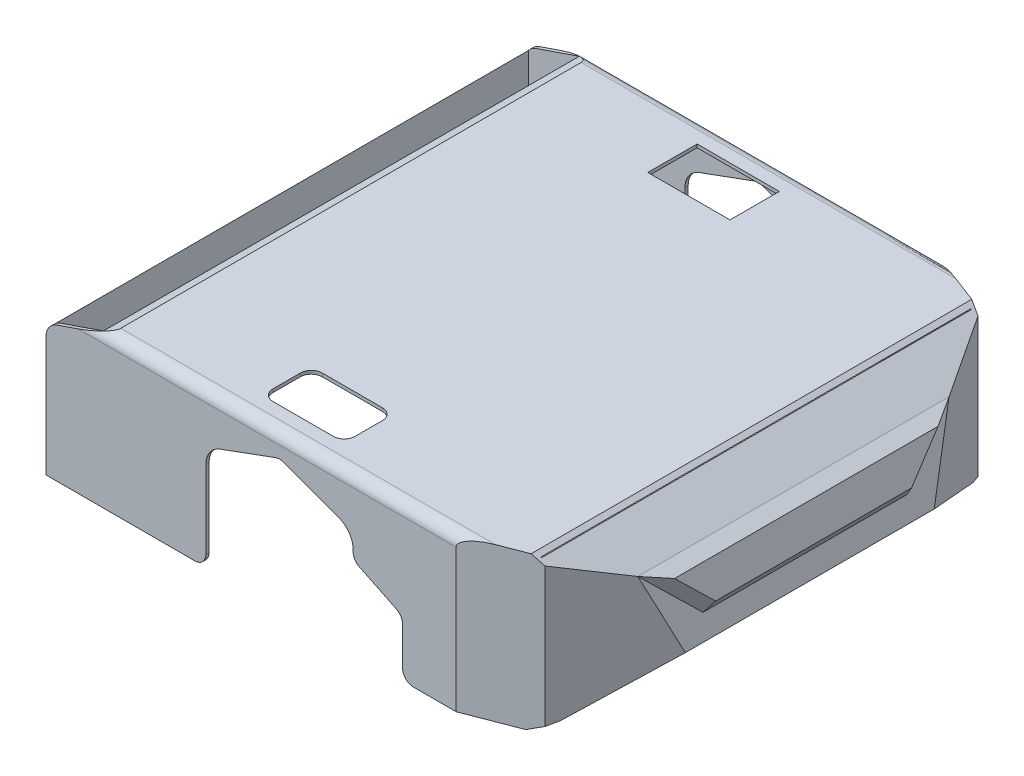
SolidWorks part; units mm, degrees
material "CA"
ref_plane "Front Plane" through (0, 0, 0) normal (0, 0, 1) x (1, 0, 0)
ref_plane "Top Plane" through (0, 0, 0) normal (0, 1, 0) x (1, 0, 0)
ref_plane "Right Plane" through (0, 0, 0) normal (1, 0, 0) x (0, 0, -1)
sketch "Sketch1" plane through (0, 0, 0) normal (0, 0, 1) x (1, 0, 0)
  line L1 (0, 0) -> (480, 0)
  line L2 (0, 0) -> (0, 140)
  line L3 (0, 140) -> (480, 140)
  line L4 (480, 0) -> (480, 140)
  dimension "D1" = 480
  dimension "D2" = 140
extrude "Boss-Extrude1" add sketch "Sketch1" along normal blind 440
sketch "Sketch2" plane through (0, 0, 440) normal (0, 0, 1) x (1, 0, 0)
  line L1 (0, 0) -> (420, 0)
  line L2 (0, 0) -> (0, 120)
  line L3 (0, 120) -> (420, 120)
  line L4 (420, 0) -> (420, 120)
  dimension "D1" = 120
  dimension "D2" = 420
sketch "Sketch3" plane through (0, 0, 440) normal (0, 0, 1) x (1, 0, 0)
  line L0 (0, 120) -> (58.2254, 140)
  line L1 (480, 140) -> (0, 140) construction
  line L2 (58.2254, 140) -> (423.4831, 140)
  line L3 (423.4831, 140) -> (461.8504, 111.6906)
  line L4 (461.8504, 111.6906) -> (480, 30.0603)
  line L5 (480, 0) -> (480, 140) construction
  line L6 (480, 30.0603) -> (420, 0)
  line L7 (0, 120) -> (0, 186.0028)
  line L8 (0, 186.0028) -> (591.5196, 186.0028)
  line L9 (591.5196, 186.0028) -> (591.5196, 0)
  line L10 (591.5196, 0) -> (420, 0)
  line L11 (480, 140) -> (0, 140) construction
extrude "Cut-Extrude2" cut sketch "Sketch3" against normal through all
chamfer "Chamfer1" distance 15 angle 60 1 edges at (480, 30.0603, 220) first distance on face at (470.9252, 70.8754, 220)
sketch "Sketch4" plane through (0, 140, 0) normal (0, 1, 0) x (1, 0, 0)
  line L2 (476.7444, -333.5325) -> (476.7444, -106.4675)
  line L5 (374.147, -440) -> (432.7602, -417.4465)
  line L7 (432.7602, -417.4465) -> (476.7444, -333.5325)
  line L8 (476.7444, -333.5325) -> (476.7444, -220)
  line L9 (476.7444, -440) -> (476.7444, 0) construction
  line L10 (476.7444, -333.5325) -> (476.7444, -220)
  line L11 (476.7444, -220) -> (259.9754, -220) construction
  line L13 (374.147, -440) -> (571.4453, -440)
  line L14 (571.4453, -440) -> (571.4453, 0)
  line L15 (571.4453, 0) -> (374.147, 0)
  line L16 (374.147, 0) -> (432.7602, -22.5535)
  line L17 (432.7602, -22.5535) -> (476.7444, -106.4675)
  line L18 (423.4831, 0) -> (58.2254, 0) construction
  point P14 (476.7444, -220)
extrude "Cut-Extrude3" cut sketch "Sketch4" against normal blind 335 contours L2 L17 L16 L15 L14 L13 L5 L7
fillet "Fillet1" radius 10 2 edges at (216.1862, 140, 0) (216.1862, 140, 440)
fillet "Fillet2" radius 15 1 edges at (0, 120, 220)
sketch "Sketch6" plane through (463.7578, 103.1116, 0) normal (0.9762, 0.217, 0) x (0, 0, -1)
  line L0 (-361.9476, 8.7884) -> (-313.0975, -39.8352)
  line L1 (-313.0975, -39.8352) -> (-126.9025, -39.8352)
  line L2 (-361.9476, 8.7884) -> (-78.0524, 8.7884)
  line L3 (-333.5325, -59.8352) -> (-106.4675, -59.8352)
  line L4 (-220, -59.8352) -> (-220, -40.6647) construction
  line L5 (-78.0524, 8.7884) -> (-361.9476, 8.7884) construction
  line L6 (-78.0524, 8.7884) -> (-126.9025, -39.8352)
  point P10 (-220, -39.8352)
  point P15 (-220, 8.7884)
  line M9 (-78.0524, 8.7884) -> (-361.9476, 8.7884)
  dimension "D1" = 20
extrude "Boss-Extrude2" add sketch "Sketch6" along direction (-0.9762, -0.217, 0) on the side of the normal blind 10 draft 42 contours L4 L1 L6 M9 | L1 L4 L2 L0 region at (466.7614, 89.6024, 220)
sketch "Sketch7" plane through (0, 0, 0) normal (0, -1, 0) x (1, 0, 0)
  line L1 (428.0503, 416.0444) -> (373.5897, 437)
  line L2 (373.5897, 437) -> (3, 437)
  line L3 (3, 437) -> (3, 3)
  line L4 (3, 3) -> (373.5897, 3)
  line L5 (373.5897, 3) -> (428.0503, 23.9556)
  line L14 (428.0503, 23.9556) -> (428.0503, 416.0444)
extrude "Cut-Extrude4" cut sketch "Sketch7" against normal offset from surface (137 mm away) 3 contours L1 L2 L3 L4 L5 L14 up to face at (293.948, 140, 220)
sketch "Sketch8" plane through (0, 140, 0) normal (0, 1, 0) x (1, 0, 0)
  line L0 (58.2254, -220) -> (508.1789, -220) construction
  line L1 (58.2254, -10) -> (58.2254, -430) construction
  line L2 (213, -58.5371) -> (213, -29.5371) construction
  line L3 (200.5, -44.0371) -> (229.5, -44.0371) construction
  line L5 (229.5, -34.5371) -> (229.5, -53.5371) construction
  line L6 (185.5, -373.4629) -> (240.5, -373.4629)
  line L7 (175.5, -66.5371) -> (250.5, -66.5371)
  line L8 (175.5, -66.5371) -> (175.5, -21.5371)
  line L9 (175.5, -21.5371) -> (250.5, -21.5371)
  line L10 (250.5, -66.5371) -> (250.5, -21.5371)
  line L11 (175.5, -66.5371) -> (250.5, -21.5371) construction
  line L12 (175.5, -21.5371) -> (250.5, -66.5371) construction
  line L13 (175.5, -383.4629) -> (175.5, -408.4629)
  line L14 (185.5, -418.4629) -> (240.5, -418.4629)
  line L15 (250.5, -383.4629) -> (250.5, -408.4629)
  arc A0 (185.5, -373.4629) -> (175.5, -383.4629) centre (185.5, -383.4629) ccw
  arc A1 (240.5, -373.4629) -> (250.5, -383.4629) centre (240.5, -383.4629) cw
  arc A2 (175.5, -408.4629) -> (185.5, -418.4629) centre (185.5, -408.4629) ccw
  arc A3 (240.5, -418.4629) -> (250.5, -408.4629) centre (240.5, -408.4629) ccw
  point P17 (213, -44.0371)
  point P25 (175.5, -373.4629)
  point P28 (250.5, -373.4629)
  point P31 (175.5, -418.4629)
  point P34 (250.5, -418.4629)
  dimension "D3" = 10
  dimension "D1" = 75
  dimension "D2" = 45
extrude "Cut-Extrude5" cut sketch "Sketch8" against normal blind 10
sketch "Sketch9" plane through (0, 0, 440) normal (0, 0, 1) x (1, 0, 0)
  line L0 (213, 48.5752) -> (213, 127) construction
  line L1 (213, 119.686) -> (158.9171, 99.8501)
  line L2 (145.8038, 81.0732) -> (145.8038, 0)
  line L3 (0, 0) -> (374.147, 0) construction
  line L4 (145.8038, 0) -> (280.1962, 0)
  line L5 (280.1962, 81.0732) -> (280.1962, 0)
  line L6 (213, 119.686) -> (267.0829, 99.8501)
  arc A1 (158.9171, 99.8501) -> (145.8038, 81.0732) centre (165.8038, 81.0732) ccw
  arc A2 (267.0829, 99.8501) -> (280.1962, 81.0732) centre (260.1962, 81.0732) cw
  point P15 (213, 0)
  point P18 (0, 0)
  dimension "D1" = 20
extrude "Cut-Extrude6" cut sketch "Sketch9" against normal blind 674
sketch "Sketch10" plane through (0, 0, 440) normal (0, 0, 1) x (1, 0, 0)
  line L0 (280.1962, 73.1231) -> (319.6001, 53.8513)
  line L1 (280.1962, 0) -> (280.1962, 81.0732) construction
  line L2 (325.2066, 44.8682) -> (325.2066, 0)
  line L3 (280.1962, 0) -> (374.147, 0) construction
  line L4 (325.2066, 0) -> (280.1962, 0)
  line L5 (280.1962, 0) -> (280.1962, 73.1231)
  arc A0 (319.6001, 53.8513) -> (325.2066, 44.8682) centre (315.2066, 44.8682) cw
  dimension "D1" = 10
extrude "Cut-Extrude7" cut sketch "Sketch10" against normal through all
fillet "Fillet3" radius 10 8 edges at (325.2066, 0, 1.5) (145.8038, 0, 1.5) (280.1962, 73.1231, 1.5) (213, 119.686, 1.5) (325.2066, 0, 438.5) (280.1962, 73.1231, 438.5) (145.8038, 0, 438.5) (213, 119.686, 438.5)
